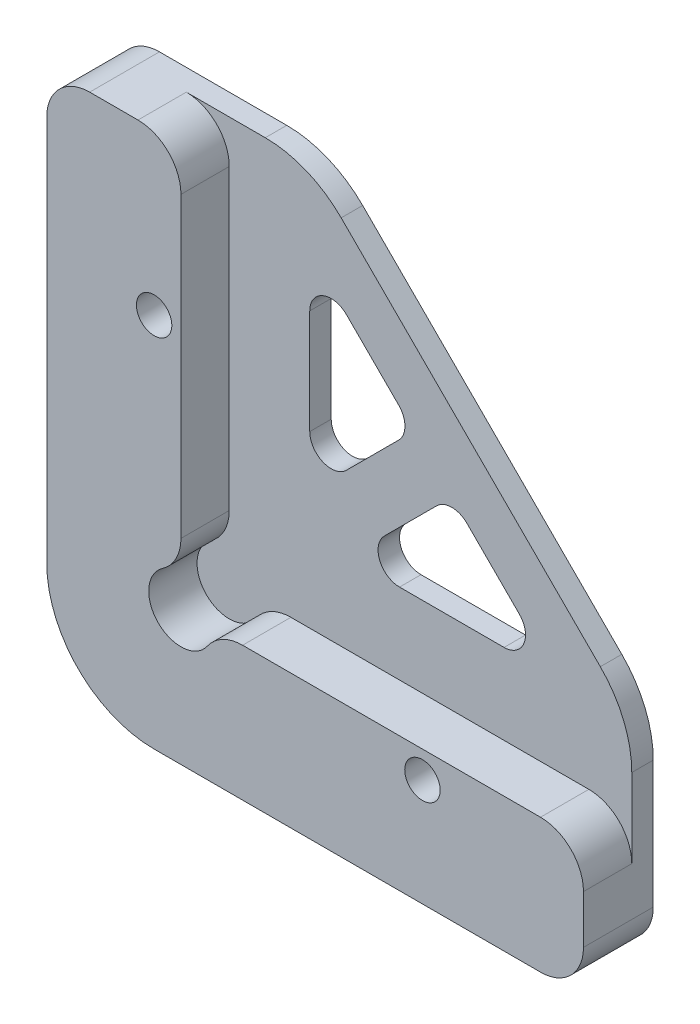
SolidWorks part; units mm, degrees
ref_plane "Front Plane" through (0, 0, 0) normal (0, 0, 1) x (1, 0, 0)
ref_plane "Top Plane" through (0, 0, 0) normal (0, 1, 0) x (1, 0, 0)
ref_plane "Right Plane" through (0, 0, 0) normal (1, 0, 0) x (0, 0, -1)
sketch "Sketch1" plane through (0, 0, 0) normal (0, 0, 1) x (1, 0, 0)
  line L0 (-20, 0) -> (-20, -10)
  line L1 (0, 0) -> (-20, 0)
  line L2 (0, 0) -> (0, 30)
  line L3 (0, 30) -> (-20, 30)
  line L4 (-20, 0) -> (-20, 30)
  line L5 (0, 0) -> (30, 0)
  line L6 (0, 0) -> (0, -20)
  line L7 (0, -20) -> (30, -20)
  line L8 (30, 0) -> (30, -20)
  line L9 (-7.5, -7.5) -> (30, -7.5)
  line L10 (-7.5, -7.5) -> (-7.5, 30)
  line L11 (-7.5, 30) -> (30, 30)
  line L12 (30, -7.5) -> (30, 30)
  line L13 (-10, -20) -> (0, -20)
  line L14 (0, 30) -> (30, 0)
  arc A0 (-20, -10) -> (-10, -20) centre (-10, -10) ccw
  circle A1 centre (-10, 15) radius 1.65
  circle A2 centre (15, -10) radius 1.65
  dimension "D5" = 10
  dimension "D7" = 3.3
  dimension "D1" = 20
  dimension "D2" = 30
  dimension "D3" = 7.5
  dimension "D4" = 7.5
  dimension "D6" = 15
  dimension "D8" = 15
extrude "Boss-Extrude1" add sketch "Sketch1" along normal blind 6.5 contours L1 L10 L3 L4 A1 | L0 A0 L13 L6 L9 L10 L1 | L9 L6 L7 L8 A2 region at (-10.5737, -10.5737, 0) region at (-13.8375, 15, 0) region at (15, -13.8375, 0)
extrude "Boss-Extrude2" add sketch "Sketch1<3>" along normal blind 2 contours L10 L1 L2 L3 | L10 L9 L6 L1 | L6 L9 L8 L5 | L14 L2 L5 region at (-3.75, 15, 0) region at (-3.75, -3.75, 0) region at (10, 10, 0) region at (15, -3.75, 0)
sketch "Sketch1<3>" plane through (0, 0, 0) normal (0, 0, 1) x (1, 0, 0) same geometry as "Sketch1"
fillet "Fillet1" radius 10 2 edges at (30, 0, 1) (0, 30, 1)
fillet "Fillet2" radius 4 4 edges at (-20, 30, 3.25) (30, -20, 3.25) (30, -7.5, 4.25) (-7.5, 30, 4.25)
sketch "Sketch2" plane through (0, 0, 6.5) normal (0, 0, 1) x (1, 0, 0)
  circle A0 centre (-7.5, -7.5) radius 3
  dimension "D1" = 6
extrude "Cut-Extrude1" cut sketch "Sketch2" against normal up to surface (4.5 mm away) up to face at (9.7788, 9.7788, 2)
fillet "Fillet3" radius 4 2 edges at (-4.5, -7.5, 4.25) (-7.5, -4.5, 4.25)
sketch "Sketch3" plane through (0, 0, 2) normal (0, 0, 1) x (1, 0, 0)
  line L0 (3.5355, 0) -> (22.9289, 0)
  line L1 (0, 0) -> (30, 0) construction
  line L2 (22.9289, 0) -> (13.2322, 9.6967)
  line L3 (0, 0) -> (0, 30) construction
  line L4 (0, 22.9289) -> (0, 3.5355)
  line L7 (0, 30) -> (30, 0) construction
  line L8 (9.6967, 13.2322) -> (0, 3.5355)
  line L9 (13.2322, 9.6967) -> (3.5355, 0)
  line L10 (9.6967, 13.2322) -> (0, 22.9289)
  dimension "D1" = 5
  dimension "D2" = 5
extrude "Cut-Extrude2" cut sketch "Sketch3" against normal blind 2
fillet "Fillet4" radius 2 6 edges at (22.9289, 0, 1) (3.5355, 0, 1) (13.2322, 9.6967, 1) (9.6967, 13.2322, 1) (0, 22.9289, 1) (0, 3.5355, 1)
